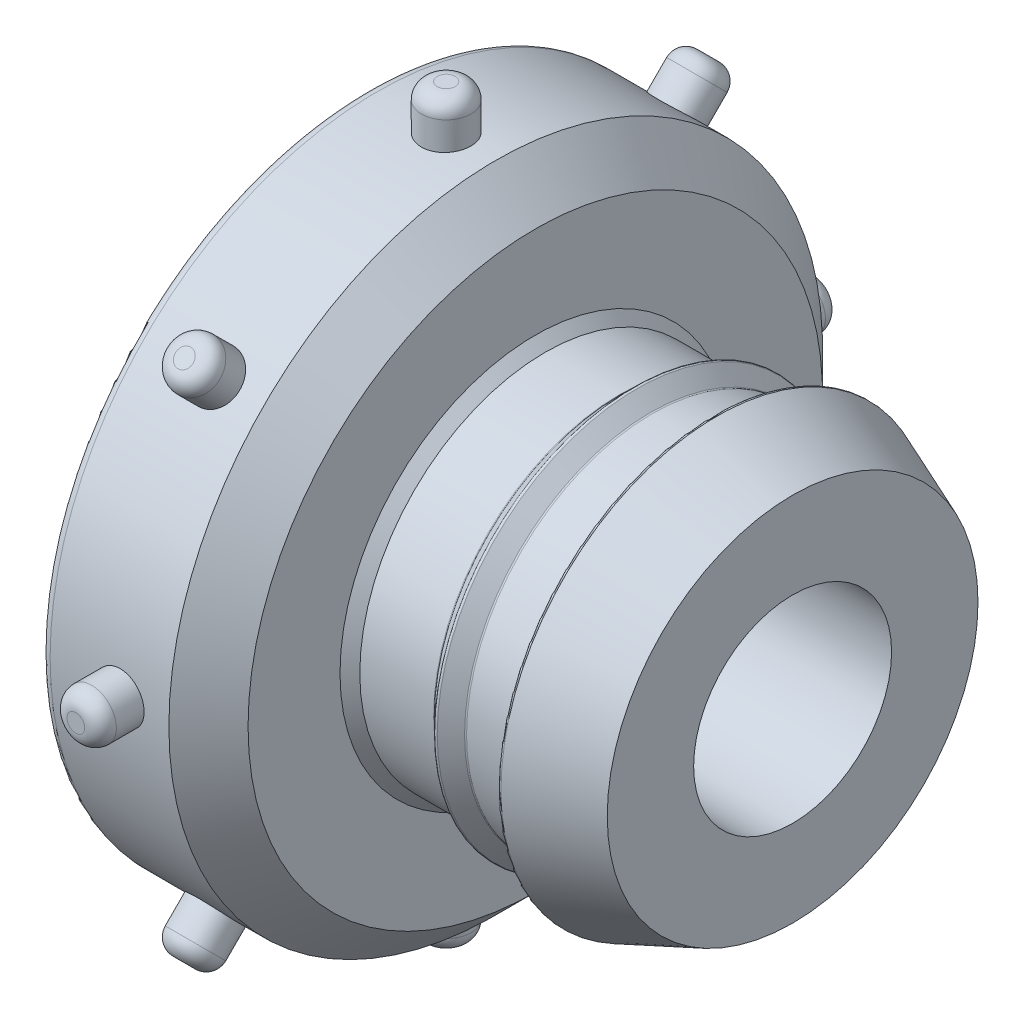
SolidWorks part; units mm, degrees
note: '?' marks a value the reader was unsure of. The reader was unsure of these and kept them because the rebuilt part matched: shared geometry of "Sketch2<3>".
ref_plane "Front Plane" through (0, 0, 0) normal (0, 0, 1) x (1, 0, 0)
ref_plane "Top Plane" through (0, 0, 0) normal (0, 1, 0) x (1, 0, 0)
ref_plane "Right Plane" through (0, 0, 0) normal (1, 0, 0) x (0, 0, -1)
sketch "Sketch1" plane through (0, 0, 0) normal (0, 1, 0) x (1, 0, 0)
  line L0 (0, 0) -> (-13, 0)
  line L1 (0, 0) -> (0, 9.365)
  line L2 (0, 9.365) -> (-3.97, 10.955)
  line L3 (-3.97, 10.955) -> (-3.97, 9.365)
  line L4 (0, 9.365) -> (-19.3321, 9.365) construction
  line L5 (-3.97, 9.365) -> (-7.15, 9.365)
  line L6 (-7.15, 9.365) -> (-7.94, 10.155)
  line L7 (-7.94, 10.155) -> (-8.73, 9.365)
  line L8 (-8.73, 9.365) -> (-13, 9.365)
  line L9 (-13, 9.365) -> (-13, 0)
  dimension "D1" = 13
  dimension "D2" = 9.365
  dimension "D3" = 1.59
  dimension "D4" = 3.97
  dimension "D5" = 7.94
  dimension "D6" = 0.79
revolve "Revolve1" add sketch "Sketch1" angle 360 about L0
sketch "Sketch2" plane through (-13, 0, 0) normal (-1, 0, 0) x (0, 0, 1)
  circle A0 centre (0, 0) radius 9.365
  circle A1 centre (0, 0) radius 9.365 construction
  circle A2 centre (0, 0) radius 5
  circle A3 centre (0, 0) radius 16.51
  circle M3 centre (0, 0) radius 9.365
  dimension "D1" = 10
  dimension "D2" = 33.02
extrude "Boss-Extrude1" add sketch "Sketch2" along normal blind 8.5 contours A3 M3 | A2 M3
ref_axis "Axis1" through (-21.5, -18.161, 0) along (0, 1, 0)?
sketch "Sketch4" plane through (-21.5, 0, 0) normal (-1, 0, 0) x (0, 0, 1)
  line L0 (0, -18.161) -> (0, 18.161) construction
  line L1 (9.09, 6.63) -> (-9.09, 6.63)
  line L2 (9.09, 6.63) -> (9.09, -6.92)
  line L3 (9.09, -6.92) -> (-9.09, -6.92)
  line L4 (-9.09, 6.63) -> (-9.09, -6.92)
  circle A1 centre (0, 0) radius 16.51 construction
  point P6 (0, 6.63)
  dimension "D1" = 18.18
  dimension "D2" = 13.55
  dimension "D3" = 6.92
extrude "Cut-Extrude1" cut sketch "Sketch4" against normal blind 7
sketch "Sketch5" plane through (-21.5, 0, 0) normal (-1, 0, 0) x (0, 0, 1)
  circle A0 centre (0, 0) radius 14.14
  dimension "D1" = 28.28
sketch "Sketch6" plane through (0, 0, 0) normal (0, 0, 1) x (1, 0, 0)
  line L0 (-21.5, 14.14) -> (-21.5, -14.14) construction
  circle A0 centre (-21.5, 14.14) radius 0.9
  point P0 (-21.5, 14.14)
  dimension "D1" = 1.8
ref_axis "Axis2" through (-35.0271, 0, 0) along (1, 0, 0)
revolve "Cut-Revolve1" cut sketch "Sketch6" angle 360 about axis through (-35.0271, 0, 0) along (1, 0, 0)
fillet "Fillet1" radius 1 1 edges at (-21.5, 0, -13.24)
ref_plane "Plane1" through (-17.5, 0, 0) normal (-1, 0, 0) x (0, 0, 1)
ref_axis "Axis3" through (-17.5, -18.161, 0) along (0, 1, 0)?
ref_plane "Plane2" through (0, 16.51, 0) normal (0, 1, 0) x (1, 0, 0)
sketch "Sketch7" plane through (0, 16.51, 0) normal (0, 1, 0) x (1, 0, 0)
  circle A0 centre (-17.5, 0) radius 1.25
  dimension "D1" = 2.5
extrude "Boss-Extrude2" add sketch "Sketch7" along normal blind 2.2 and the other way blind 2 contours A0
fillet "Fillet2" radius 0.8 1 edges at (-17.5, 18.71, 1.25)
pattern_circular "CirPattern1" count 8 over 360 about axis through (0, 0, 0) along (1, 0, 0) of "Boss-Extrude2", "Fillet2"
chamfer "Chamfer1" distance 2 angle 45 1 edges at (-13, 0, 16.51)
fillet "Fillet3" radius 0.5 1 edges at (-21.5, 0, 16.51)
fillet "Fillet4" radius 0.1 5 edges at (-8.73, 0, -9.365) (-7.94, 0, -10.155) (-7.15, 0, -9.365) (-3.97, 0, -9.365) (-3.97, 0, -10.955)
chamfer "Chamfer2" distance 0.5 angle 45 1 edges at (-13, 0, 9.365)
extrude "Cut-Extrude2" cut sketch "Sketch2<3>" against normal through all both and the other way through all contours A2
sketch "Sketch2<3>" plane through (-13, 0, 0) normal (-1, 0, 0) x (0, 0, 1) same geometry as "Sketch2"
chamfer "Chamfer3" distance 1 angle 76 1 edges at (-21.5, -6.92, 0)
sketch "Sketch8" plane through (-14.5, 0, 0) normal (-1, 0, 0) x (0, 0, 1)
  line L1 (-9.09, -6.92) -> (-5, -6.92)
  line L2 (-9.09, -6.92) -> (-9.09, 0.73)
  line L3 (-9.09, 0.73) -> (-5, 0.73)
  line L4 (-5, -6.92) -> (-5, 0.73)
  circle A0 centre (0, 0) radius 5 construction
  dimension "D1" = 7.65
extrude "Boss-Extrude3" add sketch "Sketch8" along normal blind 0.64
fillet "Fillet5" radius 0.5 2 edges at (-15.14, 0.73, -7.045) (-15.14, -3.095, -5)
equation "\"WallThick\"= 1.2'thickness of wall for printer"
equation "\"dHole\"= 3.3'diameter of screw hole"
equation "\"D3@Sketch4\"=33.02/2-9.59"
equation "\"D1@Boss-Extrude2\"=(37.42-33.02)/2"
